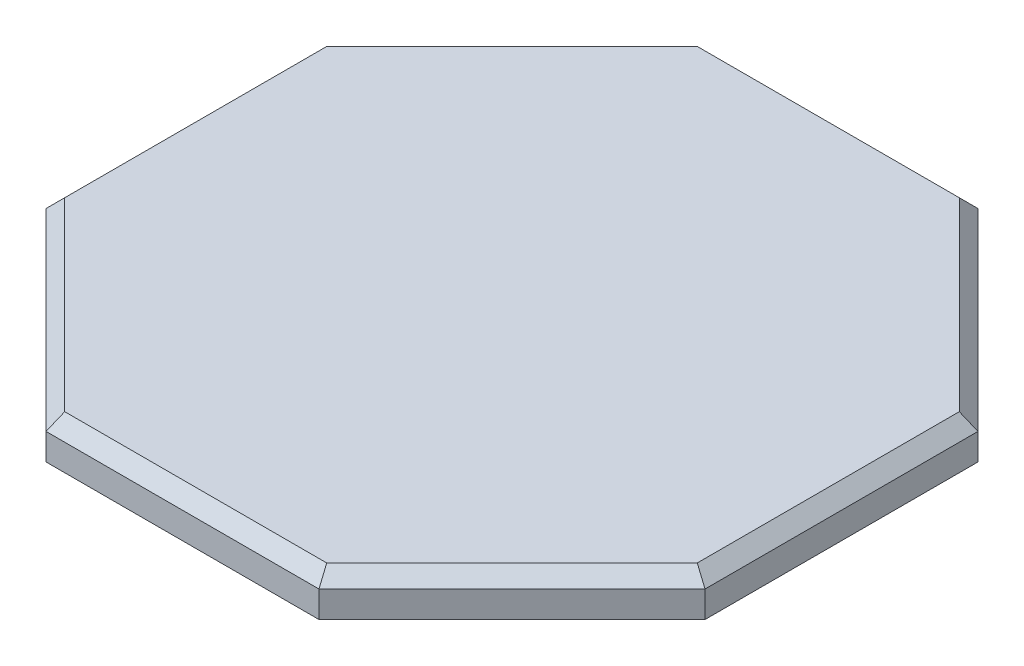
SolidWorks part; units mm, degrees
ref_plane "Plano frontal" through (0, 0, 0) normal (0, 0, 1) x (1, 0, 0)
ref_plane "Plano superior" through (0, 0, 0) normal (0, 1, 0) x (1, 0, 0)
ref_plane "Plano direito" through (0, 0, 0) normal (1, 0, 0) x (0, 0, -1)
sketch "Esboço1" plane through (0, 0, 0) normal (0, 1, 0) x (1, 0, 0)
  line L0 (30.9625, -74.75) -> (74.75, -30.9625)
  line L7 (74.75, 30.9625) -> (30.9625, 74.75)
  line L8 (30.9625, 74.75) -> (-30.9625, 74.75)
  line L9 (-30.9625, 74.75) -> (-74.75, 30.9625)
  line L10 (-74.75, 30.9625) -> (-74.75, -30.9625)
  line L11 (-74.75, -30.9625) -> (-30.9625, -74.75)
  line L12 (-30.9625, -74.75) -> (30.9625, -74.75)
  line L13 (74.75, -30.9625) -> (74.75, 30.9625)
  circle A0 centre (0, 0) radius 74.75 construction
  point P12 (74.75, 0)
  dimension "D1" = 149.5
extrude "Ressalto-extrusão2" add sketch "Esboço1" along normal blind 9
shell "Casca1" thickness 3 removed face at (0, 0, 0)
chamfer "Chanfro1" distance 3 angle 45 8 edges at (-52.8562, 9, 52.8562) (-74.75, 9, 0) (-52.8562, 9, -52.8562) (0, 9, -74.75) (52.8562, 9, -52.8562) (74.75, 9, 0) (52.8562, 9, 52.8562) (0, 9, 74.75)
